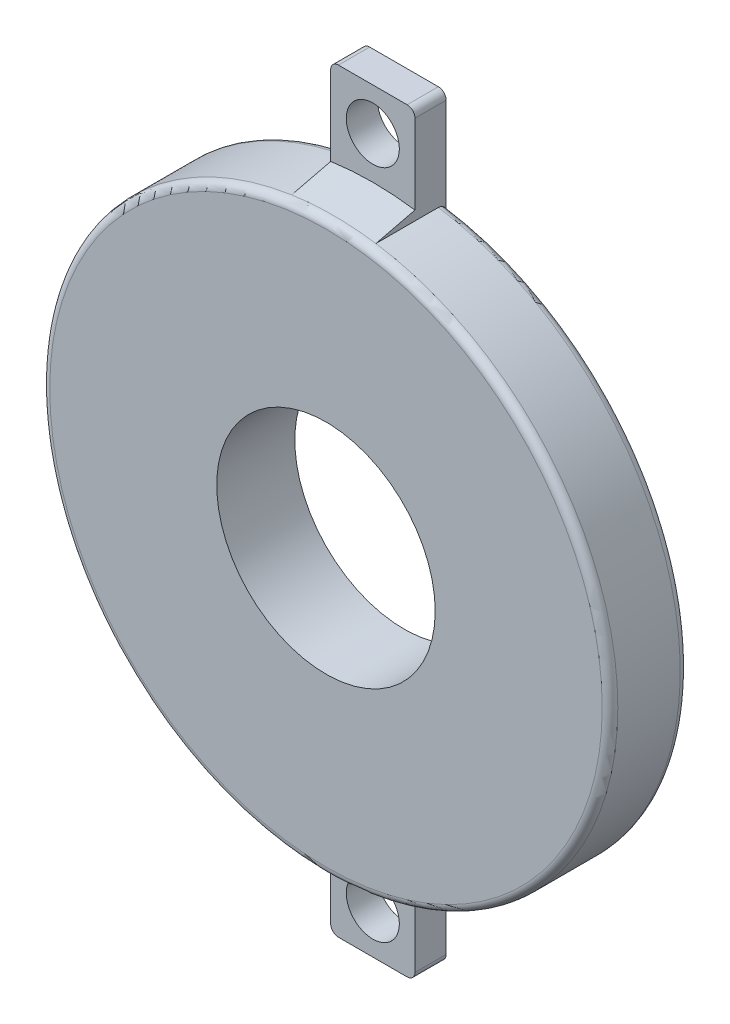
SolidWorks part; units mm, degrees
ref_plane "Alzado" through (0, 0, 0) normal (1, 0, 0) x (0, 1, 0)
ref_plane "Planta" through (0, 0, 0) normal (0, 0, 1) x (0, 1, 0)
ref_plane "Vista lateral" through (0, 0, 0) normal (0, 1, 0) x (-1, 0, 0)
sketch "Croquis2" plane through (0, 0, 0) normal (0, 0, 1) x (0, 1, 0)
  line L0 (17.9986, -2.7) -> (24.2, -2.7)
  line L1 (24.2, -2.7) -> (24.2, 2.7)
  line L2 (24.2, 2.7) -> (17.9986, 2.7)
  line L3 (18.2, 0) -> (12.9846, 0) construction
  line L4 (0, 0) -> (0, 2.6834) construction
  line L5 (-17.9986, -2.7) -> (-24.2, -2.7)
  line L6 (-24.2, -2.7) -> (-24.2, 2.7)
  line L7 (-24.2, 2.7) -> (-17.9986, 2.7)
  circle A0 centre (0, 0) radius 18.2
  circle A1 centre (21.5, 0) radius 1.7
  circle A2 centre (-21.5, 0) radius 1.7
  circle A3 centre (0, 0) radius 7
  dimension "D3" = 36.4
  dimension "D5" = 3.4
  dimension "D6" = 14
  dimension "D1" = 5.4
  dimension "D2" = 6
  dimension "D4" = 3.3
extrude "Saliente-Extruir1" add sketch "Croquis2" along normal blind 5 contours A0 region at (17.6852, 0, 0)
extrude "Saliente-Extruir2" add sketch "Croquis2<3>" along normal blind 2 contours A0 L7 L6 L5 A2 | A0 L0 L1 L2 A1 region at (1.3599, 18.2316, 0) region at (2.6178, -21.0993, 0)
sketch "Croquis2<3>" plane through (0, 0, 0) normal (0, 0, 1) x (0, 1, 0) same geometry as "Croquis2"
fillet "Redondeo1" radius 0.5 4 edges at (2.7, -24.2, 1) (-2.7, -24.2, 1) (2.7, 24.2, 1) (-2.7, 24.2, 1)
fillet "Redondeo4" radius 0.5 3 edges at (18.2, 0, 0) (-18.2, 0, 0) (18.2, 0, 5)
chamfer "Chaflán2" distance 0.6 distance2 2.5 2 edges at (0, 18.2, 2) (0, -18.2, 2) first distance on face at (1.7, 21.5, 2) first distance on face at (0, -22.0343, 2)
